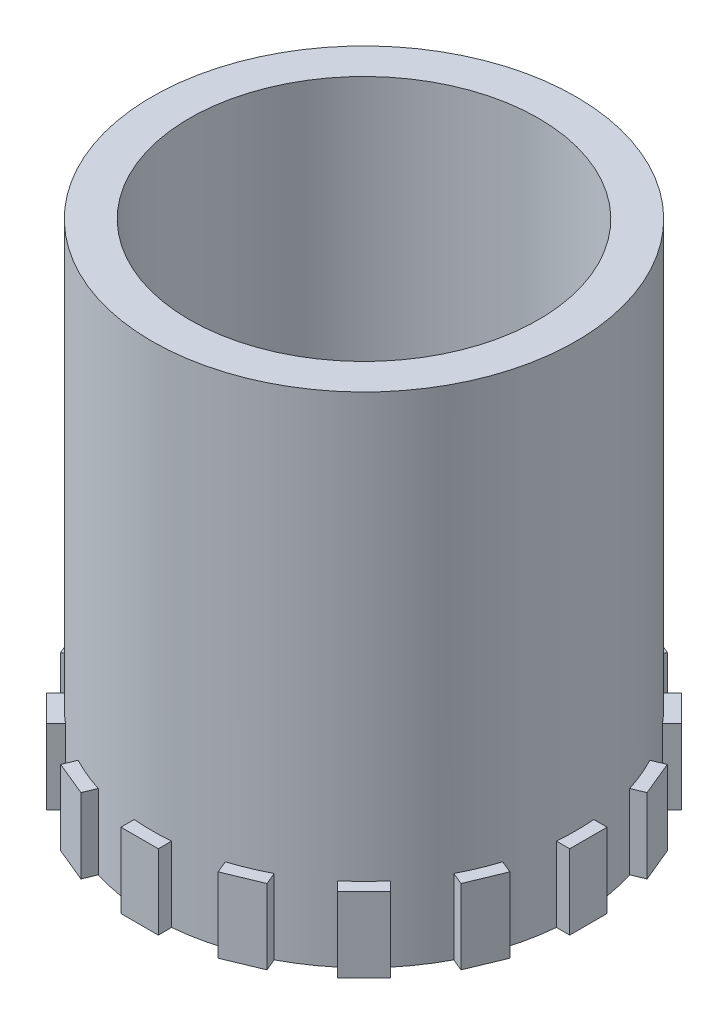
SolidWorks part; units mm, degrees
material "ABS"
ref_plane "前视基准面" through (0, 0, 0) normal (0, 0, 1) x (1, 0, 0)
ref_plane "上视基准面" through (0, 0, 0) normal (0, 1, 0) x (1, 0, 0)
ref_plane "右视基准面" through (0, 0, 0) normal (1, 0, 0) x (0, 0, -1)
sketch "草图1" plane through (0, 0, 0) normal (0, 1, 0) x (1, 0, 0)
  circle A0 centre (0, 0) radius 17
  circle A1 centre (0, 0) radius 14
  dimension "D1" = 34
  dimension "D2" = 28
extrude "凸台-拉伸1" add sketch "草图1" along normal blind 40
sketch "草图2" plane through (0, 0, 0) normal (0, -1, 0) x (-1, 0, 0)
  line L1 (-1.5, 16) -> (1.5, 16)
  line L2 (-1.5, 16) -> (-1.5, 18)
  line L3 (-1.5, 18) -> (1.5, 18)
  line L4 (1.5, 16) -> (1.5, 18)
  line L5 (-1.5, 16) -> (1.5, 18) construction
  line L6 (-1.5, 18) -> (1.5, 16) construction
  circle A0 centre (0, 0) radius 17 construction
  point P0 (0, 17)
  dimension "D1" = 3
  dimension "D2" = 2
extrude "凸台-拉伸2" add sketch "草图2" against normal blind 6
pattern_circular "阵列(圆周)1" count 16 over 360 about axis through (0, 40, 0) along (0, -1, 0) of "凸台-拉伸2"
